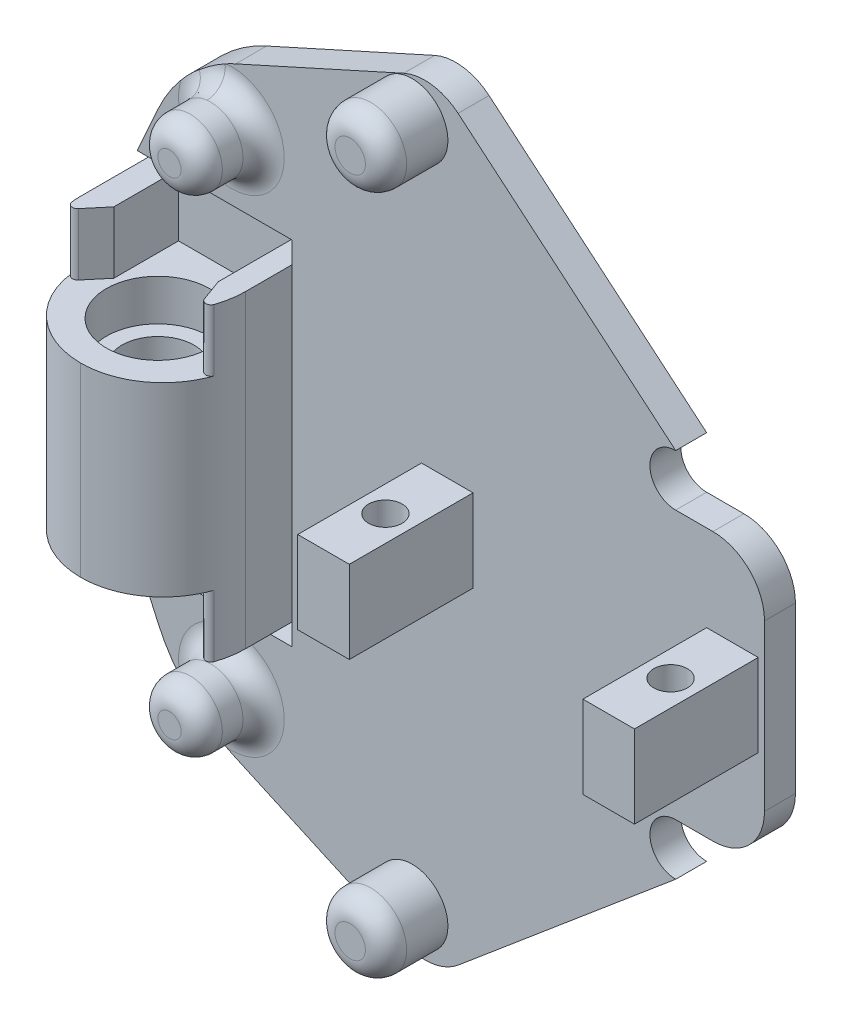
SolidWorks part; units mm, degrees
ref_plane "Alzado" through (0, 0, 0) normal (0, 0, 1) x (1, 0, 0)
ref_plane "Planta" through (0, 0, 0) normal (0, 1, 0) x (1, 0, 0)
ref_plane "Vista lateral" through (0, 0, 0) normal (1, 0, 0) x (0, 0, -1)
sketch "Croquis2" plane through (0, 0, 0) normal (0, 0, 1) x (1, 0, 0)
  line L0 (-10.8224, 56.7562) -> (13.1094, 21.0366)
  line L1 (-11.5974, 58.2365) -> (-14.2242, 64.9243)
  line L2 (-14.2242, 64.9243) -> (-52.0695, 47.8283)
  line L3 (-53.0688, 45.1822) -> (-51.6513, 42.0443)
  line L4 (13.1094, 21.0366) -> (-53.0688, 21.0366) construction
  line L5 (-53.0688, -3.109) -> (-51.6513, 0.0289)
  line L6 (-14.2242, -22.8511) -> (-52.0695, -5.755)
  line L7 (-11.5974, -16.1633) -> (-14.2242, -22.8511)
  line L8 (-10.8224, -14.683) -> (13.1094, 21.0366)
  circle A0 centre (-29.7722, 54.0212) radius 1.5
  circle A1 centre (-47.2934, 44.6229) radius 1
  circle A2 centre (-19.6168, 40.1285) radius 2
  circle A3 centre (-4.2087, 36.5366) radius 2.3724
  arc A4 (-52.0695, 47.8283) -> (-53.0688, 45.1822) centre (-51.2461, 46.0056) ccw
  arc A5 (-51.6513, 42.0443) -> (-48.9209, 41.0856) centre (-49.8287, 42.8677) ccw
  arc A6 (-48.9209, 41.0856) -> (-48.9209, 0.9876) centre (-38.7087, 21.0366) cw
  arc A7 (-11.5974, 58.2365) -> (-10.8224, 56.7562) centre (-4.3839, 61.0699) ccw
  arc A8 (-11.5974, -16.1633) -> (-10.8224, -14.683) centre (-4.3839, -18.9967) cw
  arc A9 (-51.6513, 0.0289) -> (-48.9209, 0.9876) centre (-49.8287, -0.7945) cw
  arc A10 (-52.0695, -5.755) -> (-53.0688, -3.109) centre (-51.2461, -3.9324) cw
  circle A11 centre (-4.2087, 5.5366) radius 2.3724
  circle A12 centre (-19.6168, 1.9447) radius 2
  circle A13 centre (-47.2934, -2.5497) radius 1
  circle A14 centre (-29.7722, -11.948) radius 1.5
sketch "Croquis3" plane through (0, 0, 0) normal (0, 0, 1) x (1, 0, 0)
  line L0 (-4.2087, 39.0366) -> (-27.7187, 58.8284)
  line L1 (-14.2242, 64.9243) -> (-52.0695, 47.8283) construction
  line L2 (-27.7187, 58.8284) -> (-52.0695, 47.8283)
  line L3 (-29.7722, 54.0212) -> (-26.5521, 57.8462) construction
  line L6 (13.1094, 21.0366) -> (-53.0688, 21.0366) construction
  line L7 (-53.0688, 21.0366) -> (4.3995, 21.0366) construction
  line L8 (-29.7722, -11.948) -> (-26.5521, -15.773) construction
  line L9 (-27.7187, -16.7552) -> (-52.0695, -5.755)
  line L10 (-4.2087, 3.0366) -> (-27.7187, -16.7552)
  line L12 (-4.2087, 34.0366) -> (4.3995, 34.0366)
  line L13 (-10.8224, 56.7562) -> (13.1094, 21.0366) construction
  line L14 (-4.2087, 8.0366) -> (4.3995, 8.0366)
  line L15 (-10.8224, -14.683) -> (13.1094, 21.0366) construction
  line L19 (4.3995, 34.0366) -> (4.3995, 8.0366)
  line L20 (-53.0688, 21.0366) -> (-64.0688, 21.0366) construction
  line L21 (-52.0695, -5.755) -> (-64.0688, 21.0366)
  line L22 (-64.0688, 21.0366) -> (-52.0695, 47.8283)
  arc A0 (-4.2087, 39.0366) -> (-4.2087, 34.0366) centre (-4.2087, 36.5366) ccw
  circle A4 centre (-29.7722, 54.0212) radius 2.075
  circle A6 centre (-47.2934, 44.6229) radius 1.625
  circle A8 centre (-47.2934, -2.5497) radius 1.625
  circle A10 centre (-29.7722, -11.948) radius 2.075
  arc A11 (-4.2087, 3.0366) -> (-4.2087, 8.0366) centre (-4.2087, 5.5366) cw
  dimension "D1" = 5
  dimension "D2" = 4.15
  dimension "D4" = 3.25
  dimension "D5" = 11
  dimension "D3" = 5
extrude "Saliente-Extruir1" add sketch "Croquis3" against normal blind 3
sketch "Croquis4" plane through (0, 0, 0) normal (0, 0, 1) x (1, 0, 0)
  line L0 (-23.8587, 25.6616) -> (-23.8587, 9.9116)
  line L1 (-23.8587, 9.9116) -> (-1.2087, 9.9116)
  line L2 (-1.2087, 9.9116) -> (-1.2087, 25.6616)
  line L3 (-1.2087, 25.6616) -> (3.7913, 25.6616)
  line L4 (3.7913, 25.6616) -> (3.7913, 28.1616)
  line L5 (3.7913, 28.1616) -> (-1.2087, 28.1616)
  line L6 (-1.2087, 28.1616) -> (-1.2087, 32.1616)
  line L7 (-1.2087, 32.1616) -> (-8.2087, 32.1616)
  line L8 (-8.2087, 32.1616) -> (-23.8587, 32.1616)
  line L9 (-23.8587, 32.1616) -> (-23.8587, 28.1616)
  line L10 (-23.8587, 28.1616) -> (-28.8587, 28.1616)
  line L11 (-28.8587, 28.1616) -> (-28.8587, 25.6616)
  line L12 (-28.8587, 25.6616) -> (-23.8587, 25.6616)
  line L14 (-12.5337, 9.9116) -> (-12.5337, 32.1616) construction
  line L15 (-4.2087, 8.0366) -> (4.3995, 8.0366) construction
  line L16 (-6.7087, 36.5366) -> (-6.7087, 5.5366) construction
  arc A0 (-4.2087, 39.0366) -> (-4.2087, 34.0366) centre (-4.2087, 36.5366) ccw construction
  arc A1 (-4.2087, 8.0366) -> (-4.2087, 3.0366) centre (-4.2087, 5.5366) ccw construction
  dimension "D1" = 22.25
  dimension "D2" = 22.65
  dimension "D3" = 5
  dimension "D4" = 2.5
  dimension "D5" = 5
  dimension "D6" = 4
  dimension "D7" = 22.65
  dimension "D8" = 4
  dimension "D9" = 5
  dimension "D10" = 2.5
  dimension "D11" = 5
  dimension "D12" = 15.75
  dimension "D13" = 7
  dimension "D14" = 1.5
sketch "Croquis5" plane through (0, 0, 0) normal (0, 0, 1) x (1, 0, 0)
  line L0 (-28.8587, 25.6616) -> (-23.8587, 25.6616)
  line L1 (-28.8587, 25.6616) -> (-23.8587, 25.6616) construction
  line L2 (-23.8587, 25.6616) -> (-23.8587, 17.6616)
  line L3 (-23.8587, 17.6616) -> (-28.8587, 17.6616)
  line L4 (-28.8587, 17.6616) -> (-28.8587, 25.6616)
  line L5 (-12.5337, 32.1616) -> (-12.5337, 9.9116) construction
  line L6 (3.7913, 17.6616) -> (3.7913, 25.6616)
  line L7 (-1.2087, 17.6616) -> (3.7913, 17.6616)
  line L8 (-1.2087, 25.6616) -> (-1.2087, 17.6616)
  line L9 (3.7913, 25.6616) -> (-1.2087, 25.6616)
  dimension "D1" = 5
  dimension "D2" = 8
extrude "Saliente-Extruir2" add sketch "Croquis5" along normal blind 12
sketch "Croquis6" plane through (0, 25.6616, 0) normal (0, 1, 0) x (1, 0, 0)
  line L0 (-1.2087, -12) -> (-23.8587, -12) construction
  line L1 (-12.5337, -12) -> (-12.5337, -6.075) construction
  line L2 (-28.8587, -12) -> (-28.8587, 0) construction
  line L3 (-23.8587, -12) -> (-28.8587, -12) construction
  circle A0 centre (-26.3587, -6) radius 1.625
  circle A1 centre (1.2913, -6) radius 1.625
  point P16 (-28.8587, -6)
  point P19 (-26.3587, -12)
  dimension "D1" = 3.25
extrude "Cortar-Extruir1" cut sketch "Croquis6" against normal blind 7
sketch "Croquis7" plane through (0, 0, 0) normal (0, 0, 1) x (1, 0, 0)
  line L1 (-59.0695, 30.0366) -> (-43.0695, 30.0366)
  line L2 (-59.0695, 30.0366) -> (-59.0695, 12.0366)
  line L3 (-59.0695, 12.0366) -> (-43.0695, 12.0366)
  line L4 (-43.0695, 30.0366) -> (-43.0695, 12.0366)
  line L5 (-52.0695, 21.0366) -> (-28.8587, 21.0366) construction
  line L6 (-28.8587, 25.6616) -> (-28.8587, 17.6616) construction
  line L7 (-52.0695, -5.755) -> (-52.0695, 47.8283) construction
  point P4 (-43.0695, 21.0366)
  dimension "D1" = 18
  dimension "D2" = 16
  dimension "D4" = 7
ref_plane "Plano1" through (0, 21.0366, 0) normal (0, -1, 0) x (-1, 0, 0)
sketch "Croquis10" plane through (0, 0, 0) normal (0, 0, 1) x (1, 0, 0)
  circle A0 centre (-47.2934, 44.6229) radius 1.625
  circle A1 centre (-29.7722, 54.0212) radius 2.075
  circle A3 centre (-47.2934, 44.6229) radius 3.125
  circle A4 centre (-29.7722, 54.0212) radius 3.475
  circle A5 centre (-29.7722, 54.0212) radius 2.075 construction
  circle A6 centre (-47.2934, 44.6229) radius 1.625 construction
  dimension "D1" = 1.5
  dimension "D2" = 1.4
extrude "Saliente-Extruir4" add sketch "Croquis10" along normal blind 4
sketch "Croquis11" plane through (0, 0, 4) normal (0, 0, 1) x (1, 0, 0)
  circle A0 centre (-47.2934, 44.6229) radius 3.125
  circle A1 centre (-29.7722, 54.0212) radius 3.475
  circle A2 centre (-29.7722, 54.0212) radius 3.475 construction
  circle A3 centre (-47.2934, 44.6229) radius 3.125 construction
  dimension "D1" = 0
extrude "Saliente-Extruir5" add sketch "Croquis11" along normal blind 2
fillet "Redondeo3" radius 2 3 edges at (-26.2972, 54.0212, 6) (-44.1684, 44.6229, 0) (-44.1684, 44.6229, 6)
mirror "Simetría2" about plane through (0, 21.0366, 0) normal (0, -1, 0) of "Redondeo3", "Saliente-Extruir5", "Saliente-Extruir4"
fillet "Redondeo4" radius 15 3 edges at (-52.0695, 47.8283, -1.5) (-52.0695, -5.755, -1.5) (-64.0688, 21.0366, -1.5)
fillet "Redondeo5" radius 5 4 edges at (4.3995, 34.0366, -1.5) (4.3995, 8.0366, -1.5) (-27.7187, 58.8284, -1.5) (-27.7187, -16.7552, -1.5)
sketch "Croquis14" plane through (0, 0, -3) normal (0, 0, -1) x (-1, 0, 0)
  line L0 (62.6331, 21.0366) -> (47.6331, 21.0366) construction
  line L1 (53.0688, -3.109) -> (51.6513, 0.0289) construction
  line L2 (51.6513, 42.0443) -> (53.0688, 45.1822) construction
  line L3 (53.0183, -2.9973) -> (51.6513, 0.0289)
  line L4 (51.6513, 42.0443) -> (53.0183, 45.0705)
  line L5 (61.3228, 14.9053) -> (54.3963, -0.5598) construction
  line L6 (54.3963, 42.6331) -> (61.3228, 27.1679) construction
  line L7 (61.3228, 14.9053) -> (54.3963, -0.5598)
  line L8 (54.3963, 42.6331) -> (61.3228, 27.1679)
  arc A0 (61.3228, 14.9053) -> (61.3228, 27.1679) centre (47.6331, 21.0366) ccw construction
  arc A1 (51.6513, 0.0289) -> (48.9209, 0.9876) centre (49.8287, -0.7945) ccw construction
  arc A2 (48.9209, 41.0856) -> (51.6513, 42.0443) centre (49.8287, 42.8677) ccw construction
  arc A3 (48.9209, 41.0856) -> (48.9209, 0.9876) centre (38.7087, 21.0366) ccw construction
  arc A4 (51.6513, 0.0289) -> (48.9209, 0.9876) centre (49.8287, -0.7945) ccw
  arc A5 (48.9209, 41.0856) -> (51.6513, 42.0443) centre (49.8287, 42.8677) ccw
  arc A6 (48.9209, 41.0856) -> (48.9209, 0.9876) centre (38.7087, 21.0366) ccw
  arc A8 (46.8818, -8.0985) -> (54.3963, -0.5598) centre (40.7066, 5.5714) ccw construction
  arc A9 (54.3963, 42.6331) -> (46.8818, 50.1717) centre (40.7066, 36.5018) ccw construction
  arc A10 (53.0183, -2.9973) -> (54.3963, -0.5598) centre (40.7066, 5.5714) ccw
  arc A11 (54.3963, 42.6331) -> (53.0183, 45.0705) centre (40.7066, 36.5018) ccw
  arc A12 (61.3228, 14.9053) -> (61.3228, 27.1679) centre (47.6331, 21.0366) ccw
extrude "Saliente-Extruir6" add sketch "Croquis14" along normal blind 2.5
sketch "Croquis15" plane through (0, 0, 0) normal (0, 0, 1) x (1, 0, 0)
  line L0 (-62.6331, 21.0366) -> (-47.6331, 21.0366) construction
  line L1 (-61.3228, 14.9053) -> (-56.4178, 3.9536)
  line L2 (-61.3228, 14.9053) -> (-54.3963, -0.5598) construction
  line L3 (-56.4178, 3.9536) -> (-41.4178, 3.9536)
  line L4 (-41.4178, 3.9536) -> (-41.4178, 38.1196)
  line L5 (-56.4178, 38.1196) -> (-41.4178, 38.1196)
  line L6 (-61.3228, 27.1679) -> (-56.4178, 38.1196)
  arc A0 (-61.3228, 14.9053) -> (-61.3228, 27.1679) centre (-47.6331, 21.0366) cw
  point P14 (-41.4178, 21.0366)
  dimension "D1" = 12
  dimension "D2" = 15
extrude "Cortar-Extruir5" cut sketch "Croquis15" against normal blind 2.5
sketch "Croquis16" plane through (0, 0, -2.5) normal (0, 0, 1) x (1, 0, 0)
  line L1 (-57.4178, 30.0366) -> (-41.4178, 30.0366)
  line L2 (-57.4178, 30.0366) -> (-57.4178, 12.0366)
  line L3 (-57.4178, 12.0366) -> (-41.4178, 12.0366)
  line L4 (-41.4178, 30.0366) -> (-41.4178, 12.0366)
  line L5 (-41.4178, 3.9536) -> (-41.4178, 38.1196) construction
  point P4 (-41.4178, 21.0366)
  point P7 (-41.4178, 21.0366)
  dimension "D1" = 16
  dimension "D2" = 18
extrude "Saliente-Extruir7" add sketch "Croquis16" along normal blind 15
sketch "Croquis8" plane through (0, 12.0366, 0) normal (0, -1, 0) x (1, 0, 0)
  line L0 (-57.4178, 5) -> (-49.4178, 5) construction
  line L2 (-49.4178, 5) -> (-49.4178, -2.5) construction
  line L4 (-57.4178, -2.5) -> (-41.4178, -2.5) construction
  line L5 (-57.4178, 12.5) -> (-57.4178, -2.5) construction
  circle A0 centre (-49.4178, 5) radius 5
  dimension "D1" = 10
extrude "Cortar-Extruir2" cut sketch "Croquis8" against normal blind 4
extrude "Cortar-Extruir3" cut sketch "Croquis8<2>" along normal blind 4 from surface starting at face at (-47.8178, 30.0366, 4)
sketch "Croquis8<2>" plane through (0, 12.0366, 0) normal (0, -1, 0) x (1, 0, 0) same geometry as "Croquis8"
sketch "Croquis12" plane through (0, 16.0366, 0) normal (0, -1, 0) x (1, 0, 0)
  circle A0 centre (-49.4178, 5) radius 3.5
extrude "Cortar-Extruir4" cut sketch "Croquis12" against normal up to surface (10 mm away) up to face at (-49.4178, 26.0366, 0)
fillet "Redondeo6" radius 8 2 edges at (-41.4178, 21.0366, 12.5) (-57.4178, 21.0366, 12.5)
sketch "Croquis17" plane through (0, 12.0366, 0) normal (0, -1, 0) x (1, 0, 0)
  line L0 (-49.4178, 12.5) -> (-49.4178, 0) construction
  line L1 (-49.4178, 0) -> (-56.428, 8.3545) construction
  line L2 (-49.4178, 0) -> (-45.2864, 11.3507) construction
  line L3 (-49.4178, 5) -> (-59.0575, 16.4882) construction
  line L5 (-54.9178, 3.776) -> (-54.9178, -2.5)
  line L6 (-57.4178, -2.5) -> (-41.4178, -2.5) construction
  line L7 (-57.4178, 4.5) -> (-57.4178, -2.5)
  line L8 (-57.4178, -2.5) -> (-54.9178, -2.5)
  line L9 (-49.4178, 5) -> (-45.2569, 16.4318) construction
  line L10 (-45.2569, 16.4318) -> (-40.0886, 14.5507) construction
  line L11 (-40.0886, 14.5507) -> (-42.3694, 8.2843) construction
  line L12 (-41.4178, 4.5) -> (-41.4178, -2.5)
  line L13 (-41.4178, -2.5) -> (-43.5648, -2.5)
  line L14 (-42.3694, 8.2843) -> (-43.5648, 5)
  line L15 (-43.5648, 5) -> (-43.5648, -2.5)
  line L16 (-59.0575, 16.4882) -> (-62.8877, 13.2742) construction
  line L17 (-62.8877, 13.2742) -> (-49.6515, -2.5) construction
  line L18 (-57.173, 6.4637) -> (-54.9178, 3.776)
  circle A0 centre (-49.4178, 5) radius 5 construction
  arc A1 (-49.4178, 12.5) -> (-57.4178, 4.5) centre (-49.4178, 4.5) ccw construction
  arc A2 (-41.4178, 4.5) -> (-49.4178, 12.5) centre (-49.4178, 4.5) ccw construction
  arc A3 (-42.3694, 8.2843) -> (-41.4178, 4.5) centre (-49.4178, 4.5) cw
  arc A4 (-57.4178, 4.5) -> (-57.173, 6.4637) centre (-49.4178, 4.5) cw
  dimension "D1" = 40
  dimension "D2" = 20
  dimension "D3" = 2.5
  dimension "D4" = 5.5
  dimension "D5" = 5
extrude "Saliente-Extruir8" add sketch "Croquis17" along normal blind 6
fillet "Redondeo10" radius 0.5 2 edges at (-42.3694, 9.0366, 8.2843) (-57.173, 9.0366, 6.4637)
mirror "Simetría3" about plane through (0, 21.0366, 0) normal (0, -1, 0) of "Redondeo10", "Saliente-Extruir8"
